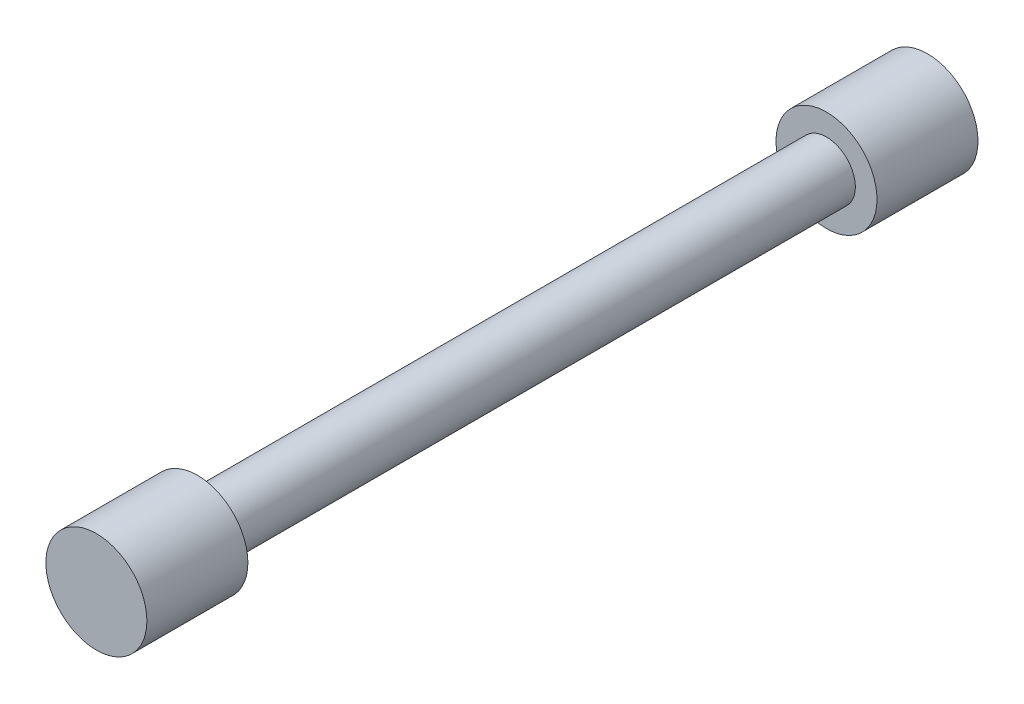
SolidWorks part; units mm, degrees
ref_plane "Front Plane" through (0, 0, 0) normal (0, 0, 1) x (1, 0, 0)
ref_plane "Top Plane" through (0, 0, 0) normal (0, 1, 0) x (1, 0, 0)
ref_plane "Right Plane" through (0, 0, 0) normal (1, 0, 0) x (0, 0, -1)
sketch "SK_Rod" plane through (0, 0, 0) normal (0, 1, 0) x (1, 0, 0)
  line L0 (0, -10) -> (0, 111.2126) construction
  line L1 (0, -7) -> (7, -7)
  line L2 (7, -7) -> (7, 7)
  line L3 (7, 7) -> (4, 7)
  line L4 (4, 7) -> (4, 94.2126)
  line L5 (4, 94.2126) -> (7, 94.2126)
  line L6 (7, 94.2126) -> (7, 108.2126)
  line L7 (7, 108.2126) -> (0, 108.2126)
  line L8 (0, 108.2126) -> (0, -7)
  dimension "P1" = 10
  dimension "P2" = 111.2126
  dimension "P3" = 7
  dimension "P4" = 7
  dimension "P5" = 7
  dimension "P6" = 7
  dimension "P7" = 7
  dimension "P8" = 4
  dimension "P9" = 7
  dimension "P10" = 4
  dimension "P11" = 94.2126
  dimension "P12" = 7
  dimension "P13" = 94.2126
  dimension "P14" = 7
  dimension "P15" = 108.2126
  dimension "P16" = 108.2126
revolve "Rod_Body" add sketch "SK_Rod" angle 360 about L0
sketch "SK_Ends" plane through (0, 0, 0) normal (0, 1, 0) x (1, 0, 0)
  point P0 (0, 0)
  point P2 (0, 101.2126)
  dimension "P1" = 101.2126
equation "\"Rod_length\" = 101.213"
